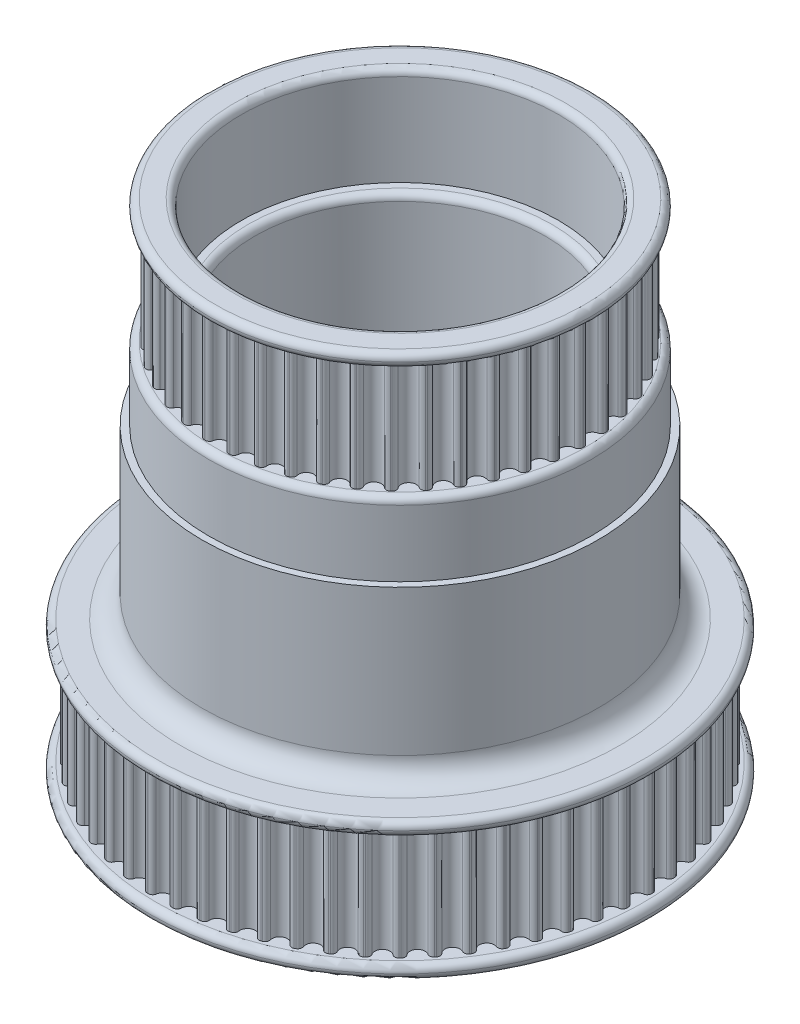
SolidWorks part; units mm, degrees
ref_plane "Front Plane" through (0, 0, 0) normal (0, 0, 1) x (1, 0, 0)
ref_plane "Top Plane" through (0, 0, 0) normal (0, 1, 0) x (1, 0, 0)
ref_plane "Right Plane" through (0, 0, 0) normal (1, 0, 0) x (0, 0, -1)
sketch "PulleyOffsets" plane through (0, 0, 0) normal (1, 0, 0) x (0, 0, -1)
  line L0 (21.4312, 0) -> (-21.4312, 0) construction
  line L1 (21.4312, 42.8625) -> (-21.4312, 42.8625) construction
  line L2 (0, 0) -> (0, 42.8625) construction
  point P7 (0, 0)
  dimension "D1" = 42.8625
ref_axis "Axis1" through (0, 34.9332, 0) along (0, -1, 0)
ref_plane "Big Pulley Plane" through (0, 0, 0) normal (0, 1, 0) x (1, 0, 0)
ref_plane "Small Pulley Plane" through (0, 42.8625, 0) normal (0, 1, 0) x (1, 0, 0)
sketch "Sketch1" plane through (0, 0, 0) normal (0, 1, 0) x (1, 0, 0)
  line L0 (0, 0) -> (0, 28.2667) construction
  line L1 (0, 0) -> (2.9202, 27.7837) construction
  circle A0 centre (0, 0) radius 28.2667 construction
  circle A1 centre (0, 0) radius 27.0467 construction
  circle A2 centre (0, 27.9367) radius 0.89 construction
  circle A5 centre (2.9202, 27.7837) radius 0.89 construction
  arc A6 (0, 27.0467) -> (0.8804, 27.8061) centre (0, 27.9367) ccw
  arc A7 (0.8804, 27.8061) -> (1.3997, 28.2321) centre (1.3749, 27.7327) cw
  arc A8 (1.559, 28.2237) -> (2.031, 27.7458) centre (1.5314, 27.7245) cw
  arc A9 (2.8272, 26.8986) -> (2.031, 27.7458) centre (2.9202, 27.7837) cw
  arc A10 (1.3997, 28.2321) -> (1.559, 28.2237) centre (0, 0) cw
  arc A11 (0, 27.0467) -> (2.8272, 26.8986) centre (0, 0) ccw
  dimension "D1" = 56.5335
  dimension "D3" = 1.78
  dimension "D4" = 0.5
  dimension "D2" = 1.22
  dimension "D5" = 6
extrude "Boss-Extrude1" add sketch "Sketch1" along normal mid plane 13 contours A6 A11 A9 A8 A7 region at (0.001, 0, -0.0192)
pattern_circular "CirPattern1" count 60 over 360 about axis through (0, 34.9332, 0) along (0, -1, 0) of "Boss-Extrude1"
sketch "Sketch2" plane through (0, 0, 0) normal (1, 0, 0) x (0, 0, -1)
  line L10 (0, 6.5) -> (29.4415, 6.5) construction
  line L11 (0, 6.5) -> (0, 8.0875) construction
  line L12 (0, 8.0875) -> (29.4415, 8.0875) construction
  line L15 (29.4415, 6.5) -> (29.4415, 8.0875) construction
  line L20 (0, 34.9332) -> (0, -6.9932) construction
  line L22 (29.4415, 8.0875) -> (0, 8.0875)
  line L23 (29.4415, 8.0875) -> (29.4415, 6.5)
  line L24 (29.4415, 6.5) -> (0, 6.5)
  line L25 (0, 8.0875) -> (0, 6.5)
  dimension "D1" = 1.5875
  dimension "D2" = 29.4415
  dimension "D3" = 6.5
revolve "Revolve3" add sketch "Sketch2" angle 360 about axis through (0, 34.9332, 0) along (0, -1, 0) region at (0, 7.2937, -14.7207)
mirror "Mirror1" about plane through (0, 0, 0) normal (0, 1, 0) of "Revolve3"
sketch "Sketch6" plane through (0, 0, 0) normal (0, 1, 0) x (1, 0, 0)
  line L0 (0, 0) -> (0, 21.582) construction
  line L1 (0, 0) -> (2.8938, 21.0541) construction
  circle A0 centre (0, 0) radius 21.582 construction
  circle A1 centre (0, 0) radius 20.362 construction
  circle A2 centre (0, 21.252) radius 0.89 construction
  circle A5 centre (2.8938, 21.0541) radius 0.89 construction
  arc A6 (0, 20.362) -> (0.8793, 21.1145) centre (0, 21.252) ccw
  arc A7 (0.8793, 21.1145) -> (1.4059, 21.5362) centre (1.3733, 21.0373) cw
  arc A8 (1.5397, 21.527) -> (2.004, 21.0376) centre (1.5041, 21.0283) cw
  arc A9 (2.7726, 20.1724) -> (2.004, 21.0376) centre (2.8938, 21.0541) cw
  arc A10 (1.4059, 21.5362) -> (1.5397, 21.527) centre (0, 0) cw construction
  arc A11 (0, 20.362) -> (2.7726, 20.1724) centre (0, 0) ccw
  arc A12 (1.4059, 21.5362) -> (1.5397, 21.527) centre (0, 0) cw
  dimension "D3" = 1.78
  dimension "D4" = 0.5
  dimension "D2" = 1.22
  dimension "D1" = 43.1641
  dimension "D5" = 7.826
extrude "Boss-Extrude2" add sketch "Sketch6" along normal mid plane 13 from surface contours A6 A11 A9 A8 A7 region at (0.0017, 0, -0.025) starting at plane "Small Pulley Plane"
pattern_circular "CirPattern2" count 46 over 360 about axis through (0, 34.9332, 0) along (0, -1, 0) of "Boss-Extrude2"
sketch "Sketch9" plane through (0, 0, 0) normal (1, 0, 0) x (0, 0, -1)
  line L1 (0, 36.3625) -> (22.7568, 36.3625)
  line L2 (0, 36.3625) -> (0, 34.775)
  line L3 (0, 34.775) -> (22.7568, 34.775)
  line L4 (22.7568, 36.3625) -> (22.7568, 34.775)
  line L6 (0, 49.3625) -> (22.7568, 49.3625)
  line L7 (0, 49.3625) -> (0, 50.95)
  line L8 (0, 50.95) -> (22.7568, 50.95)
  line L9 (22.7568, 49.3625) -> (22.7568, 50.95)
  line L10 (29.4415, 8.0875) -> (29.4415, 6.5) construction
  line L11 (0, 34.9332) -> (0, -6.9932) construction
  line L12 (21.1145, 49.3625) -> (20.362, 49.3625) construction
  line L13 (20.1641, 36.3625) -> (21.0376, 36.3625) construction
  dimension "D1" = 22.7568
revolve "Revolve4" add sketch "Sketch9" angle 360 about axis through (0, 34.9332, 0) along (0, -1, 0)
sketch "Sketch10" plane through (0, -8.0875, 0) normal (0, -1, 0) x (1, 0, 0)
  circle A0 centre (0, 0) radius 18.669
  dimension "D1" = 37.338
extrude "Cut-Extrude1" cut sketch "Sketch10" against normal through all
sketch "Sketch11" plane through (0, 50.95, 0) normal (0, 1, 0) x (1, 0, 0)
  circle A0 centre (0, 0) radius 22.5
  dimension "D1" = 45
extrude "Cut-Extrude2" cut sketch "Sketch11" against normal up to surface (16.175 mm away) flip side to cut up to face at (0, 34.775, 18.669)
sketch "Sketch12" plane through (0, 0, 0) normal (0, 0, 1) x (1, 0, 0)
  line L0 (29.4415, 8.0875) -> (-29.4415, 8.0875) construction
  line L1 (18.669, 34.775) -> (22.5, 34.775)
  line L2 (18.669, 34.775) -> (18.669, 8.0875) construction
  line L3 (18.669, 8.0875) -> (22.5, 8.0875)
  line L4 (22.5, 34.775) -> (22.5, 8.0875) construction
  line L5 (22.5, 34.775) -> (22.5, 36.3625) construction
  line L6 (22.5, 27.775) -> (22.5, 34.775)
  line L7 (22.5, 27.775) -> (23.2938, 27.775)
  line L8 (22.5, 27.775) -> (22.5, 8.0875) construction
  line L9 (22.5, 8.0875) -> (23.2938, 8.0875)
  line L10 (23.2938, 27.775) -> (23.2938, 8.0875)
  line L11 (18.669, -8.0875) -> (18.669, 8.0875) construction
  line L12 (18.669, 2.0875) -> (17.0815, 2.0875)
  line L13 (18.669, 2.0875) -> (18.669, 39.3625) construction
  line L14 (18.669, 39.3625) -> (17.0815, 39.3625)
  line L15 (17.0815, 2.0875) -> (17.0815, 39.3625)
  line L16 (-29.4415, -8.0875) -> (29.4415, -8.0875) construction
  line L18 (18.669, 2.0875) -> (18.669, 8.0875)
  line L19 (18.669, 34.775) -> (18.669, 39.3625)
  line L20 (220.55, 42.8625) -> (-220.55, 42.8625) construction
  dimension "D1" = 7
  dimension "D2" = 0.7937
  dimension "D3" = 10.175
  dimension "D5" = 1.5875
  dimension "D4" = 3.5
revolve "Revolve5" add sketch "Sketch12" angle 360 about axis through (0, 34.9332, 0) along (0, -1, 0)
fillet "Fillet1" radius 2.54 1 edges at (0, 8.0875, -23.2938)
fillet "Fillet2" radius 0.7937 11 edges at (0, 39.3625, 17.0815) (0, 50.95, -18.669) (0, -8.0875, -18.669) (0, 2.0875, 17.0815) (0, -8.0875, 29.4415) (0, 8.0875, 29.4415) (0, 50.95, 22.5) (0, 49.3625, 22.5) (0, 36.3625, -22.5) (0, 6.5, 29.4415) (0, -6.5, 29.4415)
sketch "Sketch13" plane through (0, -8.0875, 0) normal (0, -1, 0) x (1, 0, 0)
  circle A0 centre (0, 23.0188) radius 3.175
  point P2 (0, 0)
  point P4 (4.3733, 22.5995)
  dimension "D2" = 6.35
  dimension "D1" = 23.0188
extrude "Cut-Extrude3" cut sketch "Sketch13" against normal blind 3.175
equation "\"TEETH_NUM\"= 60"
equation "\"TOOTH_PITCH\"= 3mm"
equation "\"PITCH_LINE_OFFSET\"= .015in"
equation "\"DIAMETER_PER_GROOVE\"= \"OUTSIDE_DIAMETER\" / \"TEETH_NUM\" * 1in"
equation "\"PITCH_DIAMETER\"= ( ( \"TEETH_NUM\" * 3 - 1.31 ) / 3.1415 + .415 ) * 1mm"
equation "\"OUTSIDE_DIAMETER\"= \"PITCH_DIAMETER\" - \"PITCH_LINE_OFFSET\" * 2"
equation "\"D1@Sketch1\"=\"OUTSIDE_DIAMETER\""
equation "\"TOOTH_HEIGHT\"= 1.22mm"
equation "\"D2@Sketch1\"=\"TOOTH_HEIGHT\""
equation "\"TOOTH_DIAMETER\"= 1.78mm"
equation "\"INTERNAL_RADIUS\"= .5mm"
equation "\"D3@Sketch1\"=\"TOOTH_DIAMETER\""
equation "\"D5@Sketch1\"=360 / \"TEETH_NUM\""
equation "\"D4@Sketch1\"=\"INTERNAL_RADIUS\""
equation "\"D1@CirPattern1\"=\"TEETH_NUM\""
equation "\"BELT_GAP\"= 13mm"
equation "\"D2@Sketch2\"=\"PITCH_DIAMETER\"/2+1/32"
equation "\"D3@Sketch2\"=\"BELT_GAP\"/2"
equation "\"2_TEETH_NUM\"= 46"
equation "\"2_PITCH_DIAMETER\"= ( ( \"2_TEETH_NUM\" * 3 - 1.31 ) / 3.1415 + .415 ) * 1mm"
equation "\"2_OUTSIDE_DIAMETER\"= \"2_PITCH_DIAMETER\" - \"PITCH_LINE_OFFSET\" * 2"
equation "\"2_DIAMETER_PER_GROOVE\"= \"2_OUTSIDE_DIAMETER\" / \"2_TEETH_NUM\" * 1in"
equation "\"D5@Sketch6\"=360/\"2_TEETH_NUM\""
equation "\"D1@Sketch6\"=\"2_OUTSIDE_DIAMETER\""
equation "\"D2@Sketch6\"=\"TOOTH_HEIGHT\""
equation "\"D3@Sketch6\"=\"TOOTH_DIAMETER\""
equation "\"D4@Sketch6\"=\"INTERNAL_RADIUS\""
equation "\"2_BELT_GAP\"= 13mm"
equation "\"D1@CirPattern2\"=\"2_TEETH_NUM\""
equation "\"D1@Boss-Extrude2\"=\"2_BELT_GAP\""
equation "\"Pulley_OffSets\"= 1.75 - 1 / 16"
equation "\"D1@PulleyOffsets\" = \"Pulley_OffSets\""
equation "\"D1@Boss-Extrude1\"=\"BELT_GAP\""
equation "\"D1@Sketch9\"=\"2_PITCH_DIAMETER\"/2+1/32"
equation "\"bearing_hole_depth_arm_side\"= 7mm + .125in"
equation "\"D3@Sketch12\"=\"bearing_hole_depth_arm_side\""
